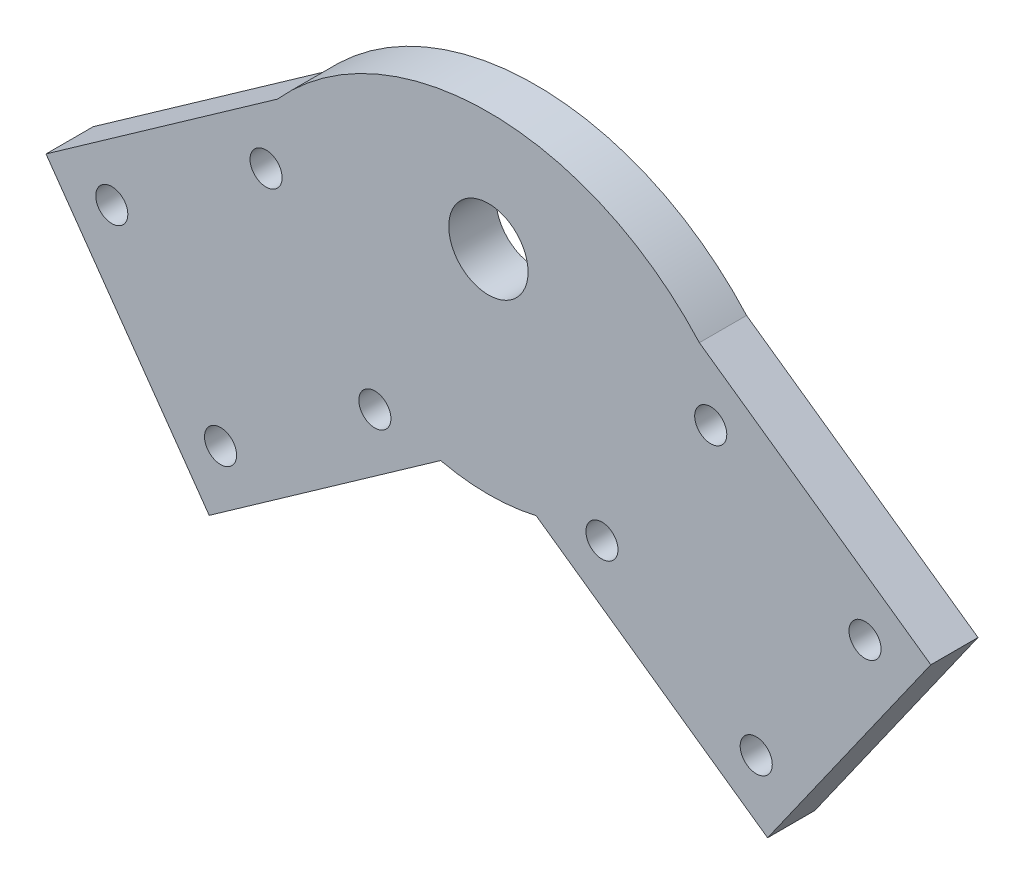
SolidWorks part; units mm, degrees
material "PLA 15%"
ref_plane "Front Plane" through (0, 0, 0) normal (0, 0, 1) x (1, 0, 0)
ref_plane "Top Plane" through (0, 0, 0) normal (0, 1, 0) x (1, 0, 0)
ref_plane "Right Plane" through (0, 0, 0) normal (1, 0, 0) x (0, 0, -1)
sketch "Sketch2" plane through (0, 0, 0) normal (0, 0, 1) x (1, 0, 0)
  line L8 (0, 0) -> (0, -22.5) construction
  line L9 (0, 0) -> (5.0614, -21.9233) construction
  line L10 (0, 0) -> (-5.0614, -21.9233) construction
  line L11 (5.0614, -21.9233) -> (22.35, 2.5941) construction
  line L12 (5.0614, -21.9233) -> (29.5789, -39.2119)
  line L13 (22.35, 2.5941) -> (46.8674, -14.6944)
  line L14 (29.5789, -39.2119) -> (46.8674, -14.6944)
  line L15 (-5.0614, -21.9233) -> (-22.35, 2.5941) construction
  line L16 (-5.0614, -21.9233) -> (-29.5789, -39.2119)
  line L17 (-22.35, 2.5941) -> (-46.8674, -14.6944)
  line L18 (-29.5789, -39.2119) -> (-46.8674, -14.6944)
  line L19 (-12.0291, -20.7185) -> (-14.517, -17.1903) construction
  line L20 (-23.5548, -4.3735) -> (-39.8997, -15.8992) construction
  line L21 (-28.374, -32.2442) -> (-39.8997, -15.8992) construction
  line L22 (-12.0291, -20.7185) -> (-28.374, -32.2442) construction
  line L23 (21.0669, -7.9017) -> (23.5548, -4.3735) construction
  line L24 (23.5548, -4.3735) -> (39.8997, -15.8992) construction
  line L25 (28.374, -32.2442) -> (39.8997, -15.8992) construction
  line L26 (12.0291, -20.7185) -> (28.374, -32.2442) construction
  line L27 (-14.517, -17.1903) -> (-21.0669, -7.9017) construction
  line L28 (-21.0669, -7.9017) -> (-23.5548, -4.3735) construction
  line L29 (-12.0291, -20.7185) -> (-23.5548, -4.3735) construction
  line L30 (12.0291, -20.7185) -> (14.517, -17.1903) construction
  line L31 (12.0291, -20.7185) -> (23.5548, -4.3735) construction
  line L32 (14.517, -17.1903) -> (21.0669, -7.9017) construction
  arc A0 (-5.0614, -21.9233) -> (5.0614, -21.9233) centre (0, 0) ccw
  arc A3 (-22.35, 2.5941) -> (-21.0669, -7.9017) centre (0, 0) ccw construction
  arc A4 (-21.0669, -7.9017) -> (-14.517, -17.1903) centre (0, 0) ccw construction
  arc A5 (-14.517, -17.1903) -> (-5.0614, -21.9233) centre (0, 0) ccw construction
  arc A6 (5.0614, -21.9233) -> (14.517, -17.1903) centre (0, 0) ccw construction
  arc A8 (14.517, -17.1903) -> (21.0669, -7.9017) centre (0, 0) ccw construction
  arc A9 (21.0669, -7.9017) -> (22.35, 2.5941) centre (0, 0) ccw construction
  circle A12 centre (0, 0) radius 4.2
  arc A15 (-22.35, 2.5941) -> (22.35, 2.5941) centre (0, -17.4179) cw
  dimension "D5" = 45
  dimension "D8" = 8.4
  dimension "D10" = 30
  dimension "D1" = 13
  dimension "D2" = 13
  dimension "D3" = 30
  dimension "D4" = 30
  dimension "D6" = 30
  dimension "D7" = 30
  dimension "D9" = 5
extrude "Boss-Extrude1" add sketch "Sketch2" along normal blind 5
hole_wizard "M3 Clearance Hole1" positions "Sketch8" profile "Sketch9" hole size "M3" standard "ANSI Metric" end condition through all
sketch "Sketch8" plane through (0, 0, 5) normal (0, 0, 1) x (1, 0, 0)
  point P0 (-39.8997, -15.8992)
  point P3 (-28.374, -32.2442)
  point P6 (-12.0291, -20.7185)
  point P9 (-23.5548, -4.3735)
  point P12 (23.5548, -4.3735)
  point P15 (28.374, -32.2442)
  point P18 (39.8997, -15.8992)
  point P21 (12.0291, -20.7185)
sketch "Sketch9" plane through (-39.8997, -15.8992, 5) normal (1, 0, 0) x (0, -1, 0)
  line L0 (0, 0) -> (0, 5)
  line L1 (0, 5) -> (1.7, 5)
  line L2 (1.7, 5) -> (1.7, 0)
  line L5 (1.7, 0) -> (0, 0)
  line L11 (0, -6.35) -> (0, 107.95) construction
  dimension "Thru Hole Dia." = 3.4
  dimension "Thru Hole Depth" = 5
